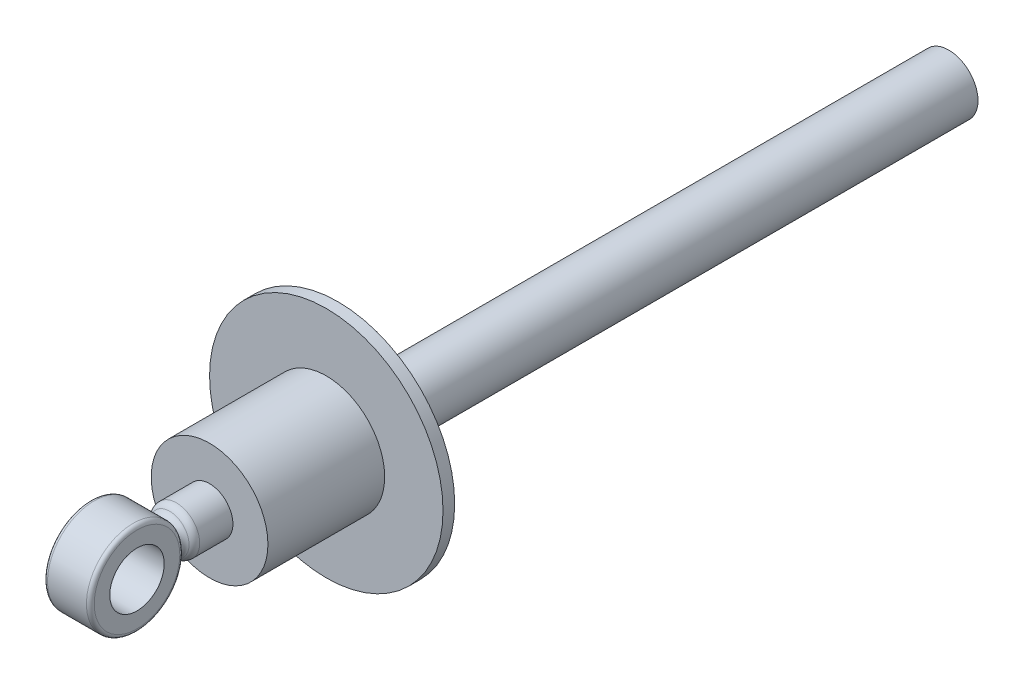
SolidWorks part; units mm, degrees
material "AISI 4140 Steel, quenched & tempered"
ref_plane "Front Plane" through (0, 0, 0) normal (1, 0, 0) x (0, 1, 0)
ref_plane "Top Plane" through (0, 0, 0) normal (0, 0, 1) x (0, 1, 0)
ref_plane "Right Plane" through (0, 0, 0) normal (0, 1, 0) x (-1, 0, 0)
sketch "Sketch1" plane through (0, 0, 0) normal (1, 0, 0) x (0, 1, 0)
  line L0 (0, 49.6932) -> (0, -80.4298) construction
  line L1 (0, 43) -> (6, 43)
  line L2 (6, 43) -> (6, 33)
  line L3 (6, 33) -> (15, 33)
  line L4 (15, 33) -> (15, 3)
  line L5 (15, 3) -> (30, 3)
  line L6 (30, 3) -> (30, 0)
  line L7 (30, 0) -> (0, 0)
  line L8 (20, 0) -> (20, -3)
  line L9 (20, -3) -> (0, -3)
  line L10 (7.5, -3) -> (7.5, -157)
  line L11 (7.5, -157) -> (0, -157)
  line L12 (0, -157) -> (0, 43)
  dimension "D1" = 60
  dimension "D2" = 40
  dimension "D3" = 12
  dimension "D4" = 15
  dimension "D5" = 30
  dimension "D6" = 3
  dimension "D7" = 3
  dimension "D8" = 190
  dimension "D9" = 160
  dimension "D10" = 200
revolve "Revolve1" add sketch "Sketch1" angle 360 about L0 region at (0, 8.175, 17.525) region at (0, 10, -1.5) region at (0, 3.75, -80)
sketch "Sketch2" plane through (0, 0, 0) normal (1, 0, 0) x (0, 1, 0)
  line L0 (6, 43) -> (-6, 43) construction
  line L1 (-4, 53.6632) -> (-4, 35.0699) construction
  line L3 (0, 57.6491) -> (0, -6.4922) construction
  line L4 (0, 45.6491) -> (0, 42.4952)
  line L5 (6, 43) -> (0, 43)
  circle A0 centre (0, 57.6491) radius 12
  circle A1 centre (0, 57.6491) radius 7
  arc A2 (-5.1429, 46.807) -> (-6, 43) centre (-6, 45) cw
  arc A3 (5.1429, 46.807) -> (6, 43) centre (6, 45) ccw
  dimension "D1" = 24
  dimension "D2" = 14
  dimension "D3" = 2
  dimension "D4" = 2
  dimension "D5" = 4
revolve "Revolve2" add sketch "Sketch2" angle 360 about L3 region at (0, 2.2912, 44.4175)
extrude "Boss-Extrude1" add sketch "Sketch2<4>" along normal mid plane 12 contours A0 A1 region at (0, -2.5612, 46.2733)
sketch "Sketch2<4>" plane through (0, 0, 0) normal (1, 0, 0) x (0, 1, 0) same geometry as "Sketch2"
fillet "Fillet1" radius 1 2 edges at (-6, 0, 45.6491) (6, 0, 45.6491)
fillet "Fillet2" radius 2 1 edges at (6, 0, 43)
